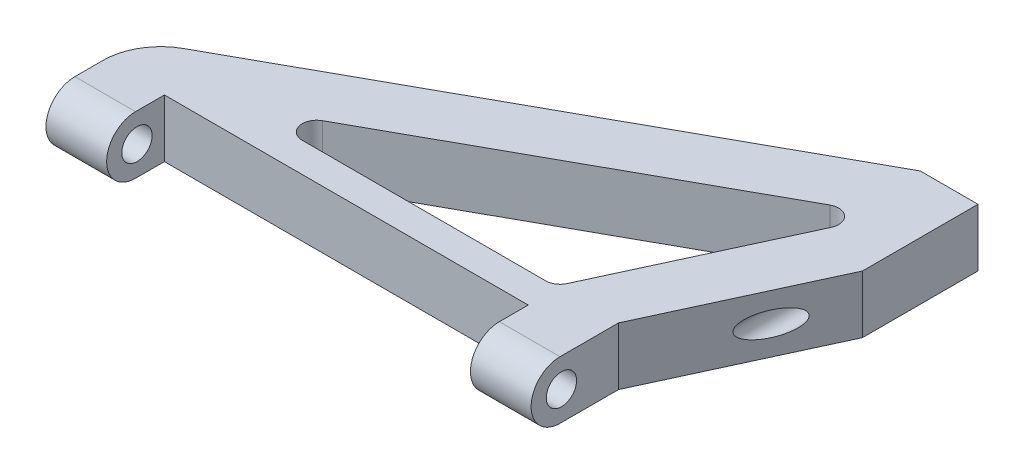
SolidWorks part; units mm, degrees
other "Markup1"
sketch "Sketch9" plane through (-9.525, 19.05, 0) normal (-0.761, 0.4779, -0.4388) x (-0.0596, 0.622, 0.7808)
material "6061-T6 (SS)"
ref_plane "Front Plane" through (0, 0, 0) normal (0, 0, 1) x (1, 0, 0)
ref_plane "Top Plane" through (0, 0, 0) normal (0, 1, 0) x (1, 0, 0)
ref_plane "Right Plane" through (0, 0, 0) normal (1, 0, 0) x (0, 0, -1)
sketch "Sketch1" plane through (0, 0, 0) normal (0, 1, 0) x (1, 0, 0)
  line L0 (0, 0) -> (0, -122) construction
  line L1 (0, 0) -> (165.875, 0) construction
  line L2 (165.875, 0) -> (165.875, -38.1) construction
  line L3 (156.35, 0) -> (175.4, 0)
  line L4 (175.4, 0) -> (175.4, -38.1)
  line L5 (0, -122) -> (0, -112) construction
  line L7 (10, -122) -> (-10, -122)
  line L12 (10, -102.95) -> (10, -122)
  line L13 (-76.2946, -112) -> (175.6699, -112) construction
  line L14 (140, -122) -> (-10, -122) construction
  line L15 (150, -122) -> (130, -122)
  line L16 (130, -122) -> (130, -102.95)
  line L17 (150, -122) -> (150, -93.1649)
  line L20 (150, -93.1649) -> (175.4, -38.1)
  line L21 (10, -102.95) -> (130, -102.95)
  line L24 (130, -102.95) -> (130, -54.7662) construction
  line L27 (157.7866, -30.8036) -> (130.2977, -90.3973)
  line L28 (151.1571, -24.6412) -> (43.4028, -84.2348)
  line L29 (45.7076, -93.1649) -> (125.9731, -93.1649)
  line L31 (-10, -92) -> (156.35, 0)
  line L32 (-10, -122) -> (-10, -92)
  line L34 (165.875, 0) -> (165.875, 30) construction
  arc A7 (45.7076, -93.1649) -> (43.4028, -84.2348) centre (45.7076, -88.4024) cw
  arc A8 (125.9731, -93.1649) -> (130.2977, -90.3973) centre (125.9731, -88.4024) ccw
  arc A9 (151.1571, -24.6412) -> (157.7866, -30.8036) centre (153.462, -28.8088) cw
  point P7 (165.875, 0)
  point P11 (70, -96.6)
  point P13 (0, -112)
  point P16 (0, -122)
  point P20 (140, -122)
  point P28 (129.021, -93.1649)
  point P36 (165.875, -35.3491)
  point P45 (162.8454, -13.5799)
  point P48 (22.05, -96.6)
  dimension "D12" = 30
  dimension "D13" = 19.05
  dimension "D14" = 19.05
  dimension "D18" = 4.7625
  dimension "D15" = 4.7625
  dimension "D2" = 15.875
  dimension "D3" = 38.1
  dimension "D4" = 38.1
  dimension "D5" = 112
  dimension "D6" = 20
  dimension "D7" = 140
  dimension "D8" = 20
  dimension "D9" = 10
  dimension "D10" = 19.05
  dimension "D11" = 19.05
  dimension "D16" = 30
extrude "Boss-Extrude1" add sketch "Sketch1" along normal blind 19.05 contours L12 L21 L16 L15 L17 L20 L4 L3 L7 region at (165.875, 0, 2.2194)
sketch "Sketch3" plane through (0, 0, 0) normal (0, 0, -1) x (-1, 0, 0)
  line L0 (-156.35, 19.05) -> (-175.4, 19.05) construction
  line L1 (-175.4, 19.05) -> (-175.4, 0) construction
  circle A0 centre (-165.875, 9.525) radius 3.9687
  dimension "D1" = 7.9375
  dimension "D3" = 9.525
  dimension "D2" = 9.525
extrude "Cut-Extrude1" cut sketch "Sketch3" against normal up to next
fillet "Fillet1" 2 edges at (0, 19.05, 122) (0, 0, 122) type full round first side face at (97.0136, 19.05, 83.3786) second side face at (97.0136, 0, 83.3786) middle face at (0, 9.525, 122)
sketch "Sketch6" plane through (150, 0, 0) normal (1, 0, 0) x (0, 0, -1)
  line L1 (-112, 0) -> (-112, 19.05) construction
  line L2 (-122, 19.05) -> (-93.1649, 19.05) construction
  circle A0 centre (-112, 9.525) radius 5
  point P4 (-112, 9.525)
  point P5 (-112, 0)
  dimension "D1" = 10
extrude "Cut-Extrude3" cut sketch "Sketch6" against normal through all
fillet "Fillet2" 2 edges at (140, 19.05, 122) (140, 0, 122) type full round first side face at (97.0136, 19.05, 81.6468) second side face at (97.0136, 0, 81.6468) middle face at (140, 9.525, 122)
fillet "Fillet6" radius 19.05 1 edges at (-10, 9.525, 92)
sketch "Sketch8" [suppressed] plane through (0, 19.05, 0) normal (0, 1, 0) x (1, 0, 0)
  line L4 (124.165, -36.1434) -> (43.4987, -83.1988) construction
  line L10 (160.5971, -158.3087) -> (103.1838, -57.8355)
  line L11 (130.8738, -89.8648) -> (115.3014, -62.613)
  line L12 (160.1788, -156.7334) -> (160.1788, 27.2514)
  line L13 (126.0432, -94.615) -> (128.1172, -94.615)
  line L14 (136.525, -92.075) -> (161.192, -5.7404) construction
  line L15 (81.7133, -27.9414) -> (112.9323, -82.5745) construction
  line L16 (156.3688, -22.6219) -> (156.3688, 0) construction
  line L17 (9.525, -98.425) -> (117.475, -98.425) construction
  line L18 (108.2246, -66.6568) -> (123.2866, -93.0152)
  line L19 (109.406, -62.3249) -> (110.9695, -61.4315)
  line L20 (107.5158, -59.0169) -> (147.6154, -36.1028)
  line L21 (149.093, -34.2184) -> (166.4066, 26.3792)
  line L34 (144.6213, -12.095) -> (144.6213, -17.9761)
  line L35 (122.2453, -32.8524) -> (41.579, -79.9078)
  line L36 (143.046, -20.7186) -> (113.4191, -38.001)
  line L37 (148.4313, 0) -> (148.4313, -50.4031) construction
  line L38 (98.8839, -33.2473) -> (3.8265, -88.6975)
  line L39 (109.0769, -36.8583) -> (106.5172, -32.4703)
  line L40 (105.7859, -38.778) -> (103.2262, -34.39)
  line L41 (104.6431, -43.1203) -> (17.108, -94.1825)
  line L45 (137.6708, -10.6216) -> (1.846, -89.8528)
  line L46 (-5.715, -103.0168) -> (-5.715, -104.14)
  line L47 (-5.715, -104.14) -> (5.715, -104.14)
  line L48 (5.715, -104.14) -> (5.715, -94.615)
  line L49 (5.715, -94.615) -> (121.285, -94.615)
  line L50 (121.285, -94.615) -> (121.285, -104.14)
  line L51 (121.285, -104.14) -> (132.715, -104.14)
  line L52 (132.715, -104.14) -> (132.715, -91.5414)
  line L53 (132.715, -91.5414) -> (157.5286, -4.6937)
  line L55 (157.7528, -3.81) -> (145.0012, -3.81)
  line L57 (139.8465, -9.3525) -> (107.6599, -28.128)
  line L61 (5.4262, -94.615) -> (15.5082, -94.615)
  line L65 (132.715, -91.5414) -> (157.5286, -4.6937)
  arc A6 (123.2866, -93.0152) -> (126.0432, -94.615) centre (126.0432, -91.44) ccw
  arc A7 (130.8738, -89.8648) -> (128.1172, -94.615) centre (128.1172, -91.44) cw
  arc A8 (110.9695, -61.4315) -> (115.3014, -62.613) centre (112.5447, -64.1882) cw
  arc A9 (109.406, -62.3249) -> (108.2246, -66.6568) centre (110.9813, -65.0816) ccw
  arc A10 (107.5158, -59.0169) -> (103.1838, -57.8355) centre (105.9405, -56.2603) cw
  arc A11 (147.6154, -36.1028) -> (149.093, -34.2184) centre (146.0402, -33.3462) ccw
  arc A12 (160.5971, -158.3087) -> (160.1788, -156.7334) centre (163.3538, -156.7334) cw
  arc A13 (160.1788, 27.2514) -> (166.4066, 26.3792) centre (163.3538, 27.2514) cw
  arc A14 (144.6213, -12.095) -> (139.8465, -9.3525) centre (141.4462, -12.095) ccw
  arc A15 (17.108, -94.1825) -> (15.5082, -94.615) centre (15.5082, -91.44) cw
  arc A16 (3.8265, -88.6975) -> (5.4262, -94.615) centre (5.4262, -91.44) ccw
  arc A17 (105.7859, -38.778) -> (104.6431, -43.1203) centre (103.0434, -40.3778) cw
  arc A18 (103.2262, -34.39) -> (98.8839, -33.2473) centre (100.4837, -35.9898) ccw
  arc A19 (106.5172, -32.4703) -> (107.6599, -28.128) centre (109.2597, -30.8705) cw
  arc A20 (109.0769, -36.8583) -> (113.4191, -38.001) centre (111.8194, -35.2585) ccw
  arc A21 (144.6213, -17.9761) -> (143.046, -20.7186) centre (141.4462, -17.9761) cw
  arc A26 (1.846, -89.8528) -> (-5.715, -103.0168) centre (9.525, -103.0168) ccw
  arc A28 (157.5286, -4.6937) -> (157.7528, -3.81) centre (142.875, -0.507) ccw
  arc A29 (137.6708, -10.6216) -> (145.0012, -3.81) centre (126.1523, 9.1243) ccw
  dimension "D4" = 3.81
  dimension "D5" = 3.175
  dimension "D3" = 3.81
  dimension "D6" = 3.175
  dimension "D7" = 3.81
  dimension "D10" = 3.175
  dimension "D2" = 3.81
  dimension "D8" = 3.81
  dimension "D9" = 3.81
  dimension "D11" = 3.81
  dimension "D12" = 3.81
  dimension "D13" = 3.81
  dimension "D15" = 43.18
  dimension "D16" = 48.7737
extrude "Cut-Extrude4" [suppressed] cut sketch "Sketch8" against normal blind 12.7 contours A21 L34 A14 L57 A19 L39 A20 L36 | L40 A18 L38 A16 L61 A15 L41 A17 | A13 L12 A12 L10 A10 L20 A11 L21 | L19 A9 L18 A6 L13 A7 L11 A8
thread "Thread2" pitch 1.0583 method cut profile "Thread Profile2" start angle 0, offset 0, length 28.575, pitch 1.0583, diameter 7.9375
ref_plane "Plane2" through (169.8437, 9.525, 0) normal (0, -1, 0) x (1, 0, 0)
sketch "Thread Profile2" plane through (169.8437, 9.525, 0) normal (0, -1, 0) x (1, 0, 0)
  line L0 (0, 0) -> (0, 1.0583) construction
  line L1 (0, 0) -> (0.5728, 0.3307)
  line L2 (0.5728, 0.3307) -> (0.5728, 0.463)
  line L3 (0.5728, 0.463) -> (0, 0.7937)
  line L4 (0.5728, 0.3969) -> (0, 0.3969) construction
  line L11 (0, 0) -> (0, 0.7937)
  point P2 (0, 0)
  dimension "Pitch" = 1.0583
  dimension "Profile_Angle" = 60
  dimension "Profile_Land" = 0.1323
  dimension "Profile_Height" = 0.5728
sketch "Sketch10" plane through (0, 0, 0) normal (1, 0, 0) x (0, 0, -1)
  point P0 (-112, 9.525)
sketch3d "3DSketch2"
  line L0 (0, 9.525, 112) -> (167.6024, 9.525, 112) construction
  circle A0 centre (150, 9.525, 112) radius 5 construction
  circle A1 centre (-10, 9.525, 112) radius 5 construction
  point P5 (155, 9.525, 112)
  point P9 (-5, 9.525, 112)
sketch "Sketch11" plane through (36.6209, 0, 66.2162) normal (-0.484, 0, -0.8751) x (-0.8751, 0, 0.484)
  line L0 (29.65, 12.7) -> (29.65, 6.35)
  line L1 (-40.5875, 3.175) -> (-11.8187, 3.175)
  line L2 (-43.7625, 12.7) -> (-43.7625, 6.35)
  line L3 (26.475, 15.875) -> (-2.2937, 15.875)
  line L4 (-120.35, 0) -> (2.7857, 0)
  line L5 (-120.35, 19.05) -> (-120.35, 0)
  line L6 (2.7857, 19.05) -> (-120.35, 19.05)
  line L7 (2.7857, 0) -> (2.7857, 19.05)
  line L9 (-120.35, 12.7) -> (-120.35, 6.35)
  line L13 (-117.175, 3.175) -> (-88.4062, 3.175)
  line L15 (26.475, 15.875) -> (-117.175, 15.875) construction
  line L16 (-117.175, 3.175) -> (26.475, 3.175) construction
  line L17 (-46.9375, 12.7) -> (-46.9375, 6.35)
  line L18 (-120.35, 19.05) -> (-120.35, 0) construction
  line L19 (29.65, 19.05) -> (-120.35, 19.05) construction
  line L20 (29.65, 19.05) -> (29.65, 0) construction
  line L21 (-120.35, 0) -> (29.65, 0) construction
  line L22 (26.475, 15.875) -> (26.475, 3.175) construction
  line L23 (-117.175, 15.875) -> (-117.175, 3.175) construction
  line L24 (-50.1125, 15.875) -> (-78.8812, 15.875)
  line L25 (-78.8812, 3.175) -> (-50.1125, 3.175)
  line L26 (-11.8187, 15.875) -> (-40.5875, 15.875)
  line L27 (-8.6437, 12.7) -> (-8.6437, 6.35)
  line L28 (-85.2312, 12.7) -> (-85.2312, 6.35)
  line L29 (-5.4687, 12.7) -> (-5.4687, 6.35)
  line L30 (-82.0562, 12.7) -> (-82.0562, 6.35)
  line L31 (-88.4062, 15.875) -> (-117.175, 15.875)
  line L32 (-2.2937, 3.175) -> (26.475, 3.175)
  arc A0 (26.475, 3.175) -> (29.65, 6.35) centre (26.475, 6.35) ccw
  arc A1 (26.475, 15.875) -> (29.65, 12.7) centre (26.475, 12.7) cw
  arc A2 (-5.4687, 12.7) -> (-2.2937, 15.875) centre (-2.2937, 12.7) cw
  arc A3 (-5.4687, 6.35) -> (-2.2937, 3.175) centre (-2.2937, 6.35) ccw
  arc A4 (-8.6437, 6.35) -> (-11.8187, 3.175) centre (-11.8187, 6.35) cw
  arc A5 (-8.6437, 12.7) -> (-11.8187, 15.875) centre (-11.8187, 12.7) ccw
  arc A6 (-43.7625, 12.7) -> (-40.5875, 15.875) centre (-40.5875, 12.7) cw
  arc A7 (-43.7625, 6.35) -> (-40.5875, 3.175) centre (-40.5875, 6.35) ccw
  arc A8 (-46.9375, 6.35) -> (-50.1125, 3.175) centre (-50.1125, 6.35) cw
  arc A9 (-46.9375, 12.7) -> (-50.1125, 15.875) centre (-50.1125, 12.7) ccw
  arc A10 (-82.0562, 12.7) -> (-78.8812, 15.875) centre (-78.8812, 12.7) cw
  arc A11 (-82.0562, 6.35) -> (-78.8812, 3.175) centre (-78.8812, 6.35) ccw
  arc A12 (-117.175, 3.175) -> (-120.35, 6.35) centre (-117.175, 6.35) cw
  arc A13 (-85.2312, 6.35) -> (-88.4062, 3.175) centre (-88.4062, 6.35) cw
  arc A14 (-85.2312, 12.7) -> (-88.4062, 15.875) centre (-88.4062, 12.7) ccw
  arc A15 (-117.175, 15.875) -> (-120.35, 12.7) centre (-117.175, 12.7) ccw
  point P20 (29.65, 3.175)
  point P31 (29.65, 15.875)
  dimension "D5" = 3.175
  dimension "D2" = 150
  dimension "D4" = 12.7
  dimension "D1" = 0
  dimension "D3" = 3.175
extrude "Cut-Extrude5" cut sketch "Sketch11" against normal offset from surface (15.875 mm away) 3.175 up to face at (97.2799, 9.525, 54.438)
move or copy body "Body-Move/Copy2" [suppressed] bodies to move or copy 105
move or copy body "Body-Move/Copy1" [suppressed] bodies to move or copy 105
